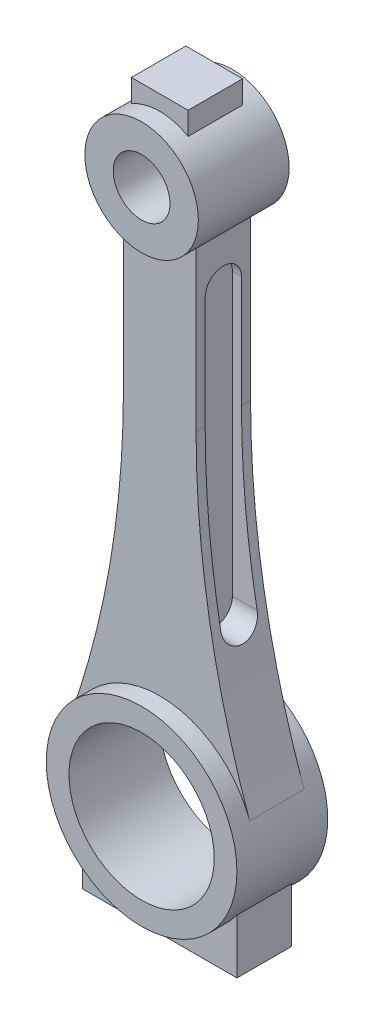
SolidWorks part; units mm, degrees
ref_plane "Front Plane" through (0, 0, 0) normal (0, 0, 1) x (1, 0, 0)
ref_plane "Top Plane" through (0, 0, 0) normal (0, 1, 0) x (1, 0, 0)
ref_plane "Right Plane" through (0, 0, 0) normal (1, 0, 0) x (0, 0, -1)
sketch "Sketch1" plane through (0, 0, 0) normal (0, 0, 1) x (1, 0, 0)
  line L0 (0, 120) -> (0, 0) construction
  line L1 (-8, 110.3953) -> (-8, 75.3953)
  line L2 (8, 110.3953) -> (8, 75.3953)
  line L3 (0, 120) -> (0, 149.6683) construction
  line L4 (-6.25, 130.8253) -> (-6.25, 135.8253)
  line L5 (-6.25, 135.8253) -> (6.25, 135.8253)
  line L6 (6.25, 135.8253) -> (6.25, 130.8253)
  line L7 (0, 0) -> (0, -38.4278) construction
  line L8 (17, -12.3288) -> (17, -24.3288)
  line L9 (17, -24.3288) -> (-17, -24.3288)
  line L10 (-17, -24.3288) -> (-17, -12.3288)
  circle A0 centre (0, 0) radius 21
  circle A1 centre (0, 0) radius 16
  circle A2 centre (0, 120) radius 12.5
  circle A3 centre (0, 120) radius 6.25
  arc A4 (-8, 75.3953) -> (-19.7874, 7.0327) centre (-212.1328, 75.3953) cw
  arc A5 (8, 75.3953) -> (19.7874, 7.0327) centre (212.1328, 75.3953) ccw
  point P15 (-8, 92.8953)
  dimension "D1" = 120
  dimension "D2" = 42
  dimension "D3" = 32
  dimension "D4" = 25
  dimension "D5" = 12.5
  dimension "D6" = 35
  dimension "D7" = 8
  dimension "D8" = 12.5
  dimension "D9" = 5
  dimension "D10" = 34
  dimension "D11" = 12
extrude "Boss-Extrude3" add sketch "Sketch1" along normal mid plane 20 contours A2 | A3 | A1 | A0
extrude "Boss-Extrude4" add sketch "Sketch1<8>" along normal mid plane 12 contours A5 L2 A2 L1 A4 A0 | A0 L10 L9 L8 region at (0, 57.8448, 0) region at (0, -21.3606, 0)
sketch "Sketch1<8>" plane through (0, 0, 0) normal (0, 0, 1) x (1, 0, 0) same geometry as "Sketch1"
extrude "Boss-Extrude5" add sketch "Sketch1<9>" along normal mid plane 12 contours A2 L6 L5 L4 region at (0, 133.8599, 0)
sketch "Sketch1<9>" plane through (0, 0, 0) normal (0, 0, 1) x (1, 0, 0) same geometry as "Sketch1"
sketch "Sketch2" plane through (0, 0, 0) normal (1, 0, 0) x (0, 0, -1)
  line L0 (0, 100) -> (0, 38) construction
  line L1 (4, 100) -> (4, 38)
  line L2 (-4, 100) -> (-4, 38)
  line L3 (-10, 120) -> (10, 120) construction
  line L4 (-10, 132.5) -> (-10, 107.5) construction
  line L5 (10, 107.5) -> (10, 132.5) construction
  arc A0 (4, 100) -> (-4, 100) centre (0, 100) ccw
  arc A1 (-4, 38) -> (4, 38) centre (0, 38) ccw
  point P3 (0, 69)
  dimension "D2" = 4
  dimension "D1" = 62
  dimension "D3" = 20
extrude "Cut-Extrude1" cut sketch "Sketch2" along normal through all from offset 6
extrude "Cut-Extrude2" cut sketch "Sketch2<2>" against normal through all from offset 6 offset against normal yes
sketch "Sketch2<2>" plane through (0, 0, 0) normal (1, 0, 0) x (0, 0, -1) same geometry as "Sketch2"
